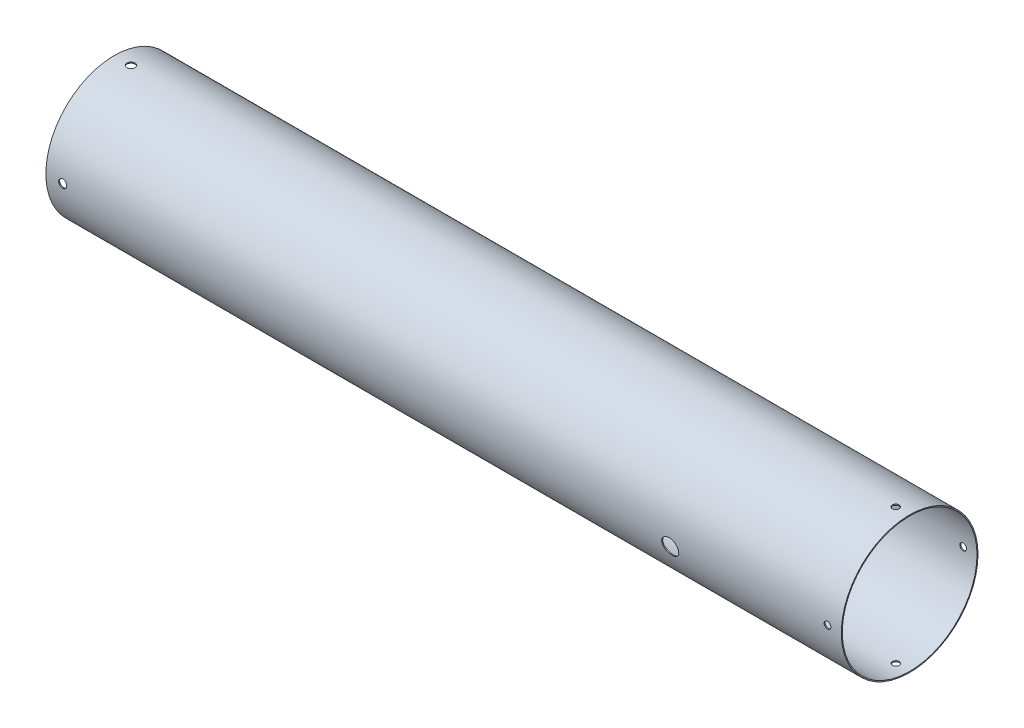
SolidWorks part; units mm, degrees
ref_plane "Front Plane" through (0, 0, 0) normal (0, 0, 1) x (1, 0, 0)
ref_plane "Top Plane" through (0, 0, 0) normal (0, 1, 0) x (1, 0, 0)
ref_plane "Right Plane" through (0, 0, 0) normal (1, 0, 0) x (0, 0, -1)
sketch "Sketch1" plane through (0, 0, 0) normal (1, 0, 0) x (0, 0, -1)
  circle A0 centre (0, 0) radius 51.562
  circle A1 centre (0, 0) radius 50.8
  dimension "D1" = 103.124
  dimension "D2" = 101.6
extrude "Boss-Extrude1" add sketch "Sketch1" along normal mid plane 600
sketch "Sketch3" plane through (0, 0, 0) normal (0, 0, 1) x (1, 0, 0)
  line L0 (300, -51.562) -> (300, 51.562) construction
  circle A1 centre (170.18, -8.89) radius 6.35
  dimension "D2" = 12.7
  dimension "D3" = 8.89
  dimension "D1" = 129.82
extrude "Cut-Extrude1" cut sketch "Sketch3" against normal through all both and the other way through all
sketch "Sketch4" plane through (0, 0, 0) normal (0, 0, 1) x (1, 0, 0)
  line L0 (300, -51.562) -> (300, 51.562) construction
  line L1 (-300, 51.562) -> (-300, -51.562) construction
  circle A0 centre (289.586, 0) radius 2.54
  circle A1 centre (-287.3, 0) radius 3.048
  dimension "D2" = 5.08
  dimension "D3" = 6.096
  dimension "D1" = 10.414
  dimension "D4" = 12.7
extrude "Cut-Extrude2" cut sketch "Sketch4" against normal through all both and the other way through all contours A1 | A0 region at (-287.3, 0, 0)
pattern_circular "CirPattern1" count 2 every 90 about axis through (300, 0, 0) along (-1, 0, 0) of "Cut-Extrude2"
